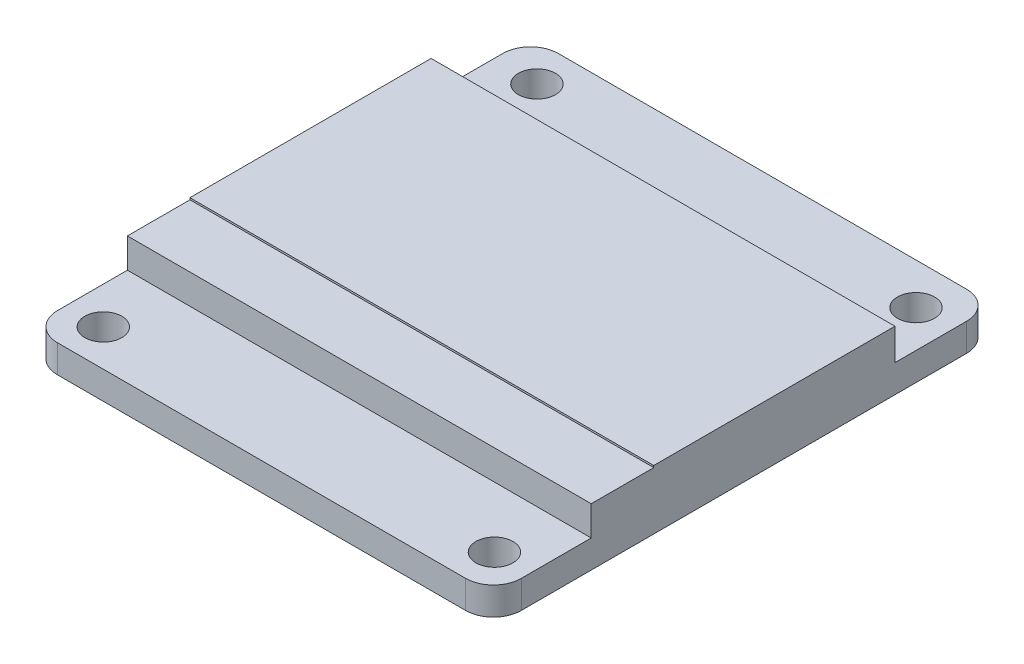
SolidWorks part; units mm, degrees
ref_plane "前视基准面" through (0, 0, 0) normal (0, 0, 1) x (1, 0, 0)
ref_plane "上视基准面" through (0, 0, 0) normal (0, 1, 0) x (1, 0, 0)
ref_plane "右视基准面" through (0, 0, 0) normal (1, 0, 0) x (0, 0, -1)
sketch "草图2" plane through (0, 0, 0) normal (0, 1, 0) x (1, 0, 0)
  line L1 (-118.2575, 92.3321) -> (-96.2575, 92.3321)
  line L2 (-119.7575, 90.8321) -> (-119.7575, 66.8321)
  line L3 (-118.2575, 65.3321) -> (-96.2575, 65.3321)
  line L4 (-94.7575, 90.8321) -> (-94.7575, 66.8321)
  arc A0 (-96.2575, 92.3321) -> (-94.7575, 90.8321) centre (-96.2575, 90.8321) cw
  arc A1 (-96.2575, 65.3321) -> (-94.7575, 66.8321) centre (-96.2575, 66.8321) ccw
  arc A2 (-119.7575, 66.8321) -> (-118.2575, 65.3321) centre (-118.2575, 66.8321) ccw
  arc A3 (-118.2575, 92.3321) -> (-119.7575, 90.8321) centre (-118.2575, 90.8321) ccw
  point P6 (-94.7575, 92.3321)
  point P9 (-94.7575, 65.3321)
  point P14 (-119.7575, 92.3321)
  dimension "D3" = 1.5
  dimension "D4" = 1.5
  dimension "D1" = 25
  dimension "D2" = 27
extrude "凸台-拉伸1" add sketch "草图2" along normal blind 1.5
sketch "草图3" plane through (0, 1.5, 0) normal (0, 1, 0) x (1, 0, 0)
  line L0 (-96.2575, 92.3321) -> (-118.2575, 92.3321) construction
  line L1 (-94.7575, 66.8321) -> (-94.7575, 90.8321) construction
  line L2 (-118.2575, 65.3321) -> (-96.2575, 65.3321) construction
  line L3 (-119.7575, 90.8321) -> (-119.7575, 66.8321) construction
  circle A0 centre (-117.413, 90.3321) radius 1
  circle A1 centre (-96.7575, 90.108) radius 1
  circle A2 centre (-96.7044, 67.3321) radius 1
  circle A3 centre (-117.7575, 67.3032) radius 1
  dimension "D5" = 2
  dimension "D1" = 2
  dimension "D2" = 2
  dimension "D3" = 2
  dimension "D4" = 2
extrude "切除-拉伸1" cut sketch "草图3" against normal through all
sketch "草图4" plane through (0, 1.5, 0) normal (0, 1, 0) x (1, 0, 0)
  line L0 (-119.7575, 90.8321) -> (-119.7575, 66.8321) construction
  line L1 (-119.7575, 86.9721) -> (-94.7575, 86.9721)
  line L2 (-119.7575, 86.9721) -> (-119.7575, 70.6021)
  line L3 (-119.7575, 70.6021) -> (-94.7575, 70.6021)
  line L4 (-94.7575, 86.9721) -> (-94.7575, 70.6021)
  line L5 (-94.7575, 66.8321) -> (-94.7575, 90.8321) construction
  line L6 (-96.2575, 92.3321) -> (-118.2575, 92.3321) construction
  dimension "D1" = 5.36
  dimension "D2" = 16.37
extrude "凸台-拉伸2" add sketch "草图4" along normal blind 1.6
sketch "草图5" plane through (0, 3.1, 0) normal (0, 1, 0) x (1, 0, 0)
  line L0 (-94.7575, 70.6021) -> (-94.7575, 86.9721) construction
  line L1 (-119.7575, 86.9721) -> (-94.7575, 86.9721)
  line L2 (-119.7575, 86.9721) -> (-119.7575, 73.9721)
  line L3 (-119.7575, 73.9721) -> (-94.7575, 73.9721)
  line L4 (-94.7575, 86.9721) -> (-94.7575, 73.9721)
  dimension "D1" = 13
extrude "凸台-拉伸3" add sketch "草图5" along normal blind 0.1
